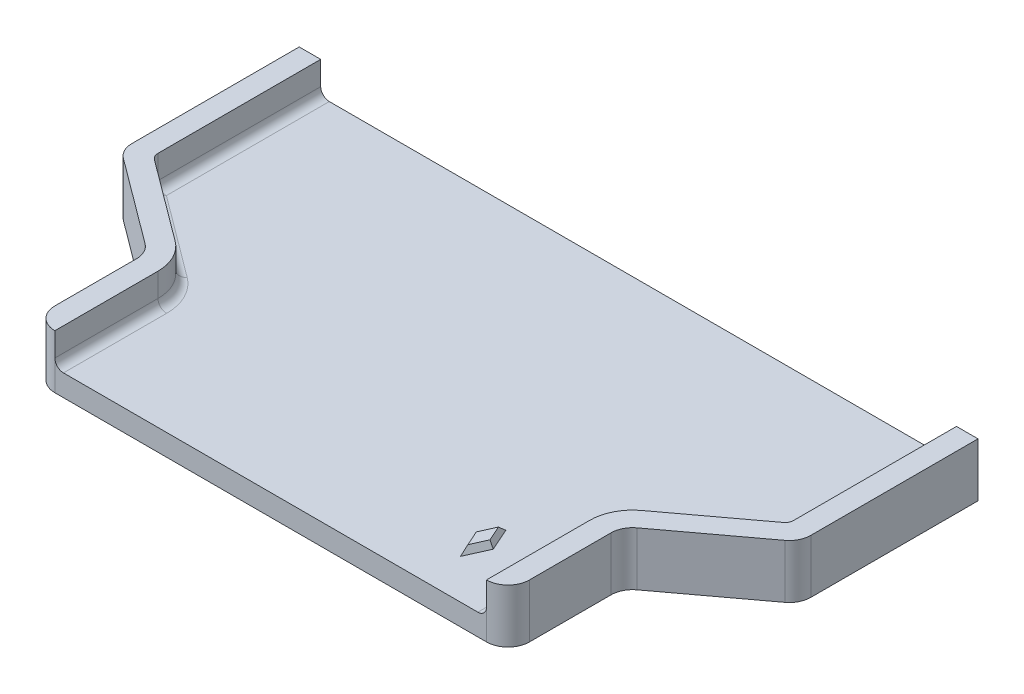
SolidWorks part; units mm, degrees
ref_plane "Front Plane" through (0, 0, 0) normal (0, 0, 1) x (1, 0, 0)
ref_plane "Top Plane" through (0, 0, 0) normal (0, 1, 0) x (1, 0, 0)
ref_plane "Right Plane" through (0, 0, 0) normal (1, 0, 0) x (0, 0, -1)
sketch "Sketch1" plane through (0, 0, 0) normal (0, 1, 0) x (1, 0, 0)
  line L0 (-14.6023, -43.4803) -> (-65.6105, -43.4803)
  line L1 (-68.1505, -40.9403) -> (-68.1505, -31.2913)
  line L2 (-69.1741, -29.2537) -> (-79.1892, -21.8006)
  line L3 (-80.2127, -19.7629) -> (-80.2127, 0)
  line L4 (-80.2127, 0) -> (0, 0)
  line L6 (0, -19.7629) -> (0, 0)
  line L7 (-11.0387, -29.2537) -> (-1.0236, -21.8006)
  line L8 (-12.0623, -40.9403) -> (-12.0623, -31.2913)
  arc A0 (-12.0623, -40.9403) -> (-14.6023, -43.4803) centre (-14.6023, -40.9403) cw
  arc A1 (-65.6105, -43.4803) -> (-68.1505, -40.9403) centre (-65.6105, -40.9403) cw
  arc A2 (-11.0387, -29.2537) -> (-12.0623, -31.2913) centre (-9.5223, -31.2913) ccw
  arc A3 (0, -19.7629) -> (-1.0236, -21.8006) centre (-2.54, -19.7629) cw
  arc A4 (-68.1505, -31.2913) -> (-69.1741, -29.2537) centre (-70.6905, -31.2913) ccw
  arc A5 (-79.1892, -21.8006) -> (-80.2127, -19.7629) centre (-77.6727, -19.7629) cw
  point P11 (-40.1064, -43.4803)
  dimension "D1" = 2.54
  dimension "D2" = 2.54
extrude "Extrude1" add sketch "Sketch1" along normal blind 6.35
shell "Shell1" thickness 2.54 removed face at (-40.1064, 3.175, 43.4803) removed face at (-40.1064, 3.175, 0) removed face at (-40.1064, 6.35, 26.7221)
fillet "Fillet2" radius 1.016 10 edges at (-77.6727, 4.445, 19.7629) (-77.6727, 2.54, 9.8815) (-72.6652, 2.54, 23.4894) (-66.151, 2.54, 29.011) (-65.6105, 2.54, 37.3858) (-2.54, 4.445, 19.7629) (-2.54, 2.54, 9.8815) (-7.5475, 2.54, 23.4894) (-14.0617, 2.54, 29.011) (-14.6023, 2.54, 37.3858)
ref_plane "Plane1" through (0, 2.54, 0) normal (0, 1, 0) x (-1, 0, 0)
sketch "Sketch3" plane through (0, 2.54, 0) normal (0, 1, 0) x (-1, 0, 0)
  line L1 (22.3565, 33.4491) -> (21.1579, 36.1227)
  line L2 (22.3565, 38.7964) -> (21.1579, 36.1227)
  line L3 (22.3565, 38.7964) -> (23.555, 36.1227)
  line L4 (23.555, 36.1227) -> (22.3565, 33.4491)
  point P0 (22.3565, 36.1227)
extrude "Extrude2" add sketch "Sketch3" along normal blind 0.762 draft 25
sketch "Sketch5" plane through (0, 2.54, 0) normal (0, 1, 0) x (-1, 0, 0)
  line L1 (61.5377, 17.5535) -> (70.6202, 17.5535)
  line L2 (18.675, 41.1049) -> (61.5377, 41.1049)
  line L3 (18.675, 41.1049) -> (18.675, 17.5535)
  line L4 (18.675, 17.5535) -> (9.5926, 17.5535)
  line L5 (9.5926, 17.5535) -> (9.5926, 4.9779)
  line L6 (70.6202, 17.5535) -> (70.6202, 4.9779)
  line L7 (9.5926, 4.9779) -> (70.6202, 4.9779)
  line L9 (61.5377, 41.1049) -> (61.5377, 17.5535)
  point P6 (40.1064, 24.5667)
  point P12 (40.1064, 24.5667)
  dimension "D1" = 9.5926
  dimension "D2" = 18.675
  dimension "D3" = 41.1049
  dimension "D4" = 61.5377
  dimension "D5" = 70.6202
  dimension "D6" = 4.9779
  dimension "D7" = 9.525
  dimension "D8" = 9.525
